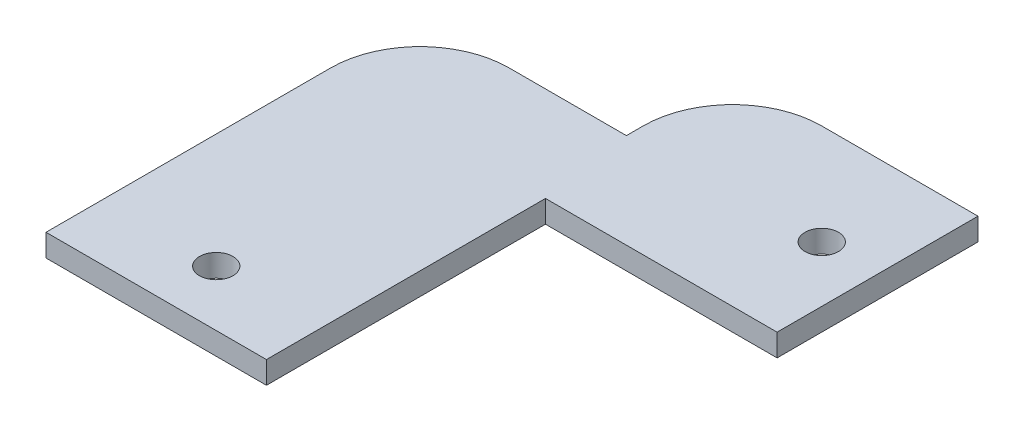
SolidWorks part; units mm, degrees
ref_plane "Front Plane" through (0, 0, 0) normal (0, 0, 1) x (1, 0, 0)
ref_plane "Top Plane" through (0, 0, 0) normal (0, 1, 0) x (1, 0, 0)
ref_plane "Right Plane" through (0, 0, 0) normal (1, 0, 0) x (0, 0, -1)
sketch "Sketch1" plane through (0, 0, 0) normal (0, 1, 0) x (1, 0, 0)
  line L0 (0, 0) -> (19.75, 0)
  line L1 (19.75, 0) -> (19.75, 25)
  line L2 (19.75, 25) -> (40.5, 25)
  line L3 (40.5, 25) -> (40.5, 43)
  line L4 (40.5, 43) -> (26.5, 43)
  line L5 (18.5, 35) -> (18.5, 33.5)
  line L6 (18.5, 33.5) -> (8, 33.5)
  line L7 (0, 25.5) -> (0, 0)
  circle A0 centre (10.25, 5) radius 1.5
  circle A1 centre (35.5, 34) radius 1.5
  arc A2 (8, 33.5) -> (0, 25.5) centre (8, 25.5) ccw
  arc A3 (26.5, 43) -> (18.5, 35) centre (26.5, 35) ccw
  dimension "D2" = 3
  dimension "D6" = 3
  dimension "D13" = 8
  dimension "D14" = 8
  dimension "D1" = 28.5
  dimension "D3" = 5
  dimension "D4" = 10.25
  dimension "D5" = 9.5
  dimension "D7" = 9
  dimension "D8" = 9
  dimension "D9" = 9.5
  dimension "D10" = 5
  dimension "D11" = 18.5
  dimension "D12" = 17
extrude "Boss-Extrude1" add sketch "Sketch1" along normal blind 2
